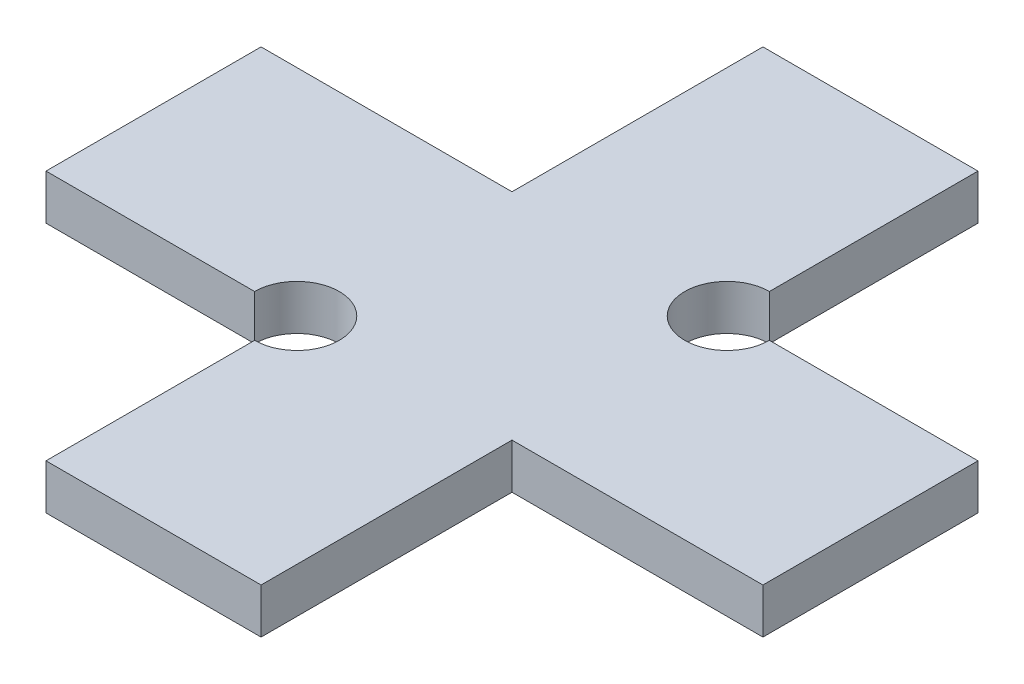
SolidWorks part; units mm, degrees
ref_plane "Front Plane" through (0, 0, 0) normal (0, 0, 1) x (1, 0, 0)
ref_plane "Top Plane" through (0, 0, 0) normal (0, 1, 0) x (1, 0, 0)
ref_plane "Right Plane" through (0, 0, 0) normal (1, 0, 0) x (0, 0, -1)
sketch "Sketch1" plane through (0, 0, 0) normal (0, 1, 0) x (1, 0, 0)
  line L1 (3.81, -12.7) -> (-3.81, -12.7)
  line L2 (3.81, -12.7) -> (3.81, 12.7)
  line L3 (3.81, 12.7) -> (-3.81, 12.7)
  line L4 (-3.81, -12.7) -> (-3.81, 12.7)
  line L5 (3.81, -12.7) -> (-3.81, 12.7) construction
  line L6 (3.81, 12.7) -> (-3.81, -12.7) construction
  line L7 (12.7, -3.81) -> (-12.7, -3.81)
  line L8 (12.7, -3.81) -> (12.7, 3.81)
  line L9 (12.7, 3.81) -> (-12.7, 3.81)
  line L10 (-12.7, -3.81) -> (-12.7, 3.81)
  line L11 (12.7, -3.81) -> (-12.7, 3.81) construction
  line L12 (12.7, 3.81) -> (-12.7, -3.81) construction
  circle A0 centre (3.81, 3.81) radius 1.5
  circle A1 centre (-3.81, -3.81) radius 1.5
  point P0 (0, 0)
  point P6 (0, 0)
  dimension "D5" = 3
  dimension "D6" = 3
  dimension "D1" = 25.4
  dimension "D2" = 7.62
  dimension "D3" = 7.62
  dimension "D4" = 25.4
extrude "Boss-Extrude1" add sketch "Sketch1" along normal blind 1.6 contours A1 L4 L9 L10 L7 | A1 L7 L2 A0 L9 L4 | A1 L4 L1 L2 L7 | A0 L2 L7 L8 L9 | A0 L2 L3 L4 L9 region at (0.085, 0, 8.357) region at (0, 0, 0) region at (8.357, 0, 0.085) region at (-8.357, 0, -0.085) region at (-0.085, 0, -8.357)
